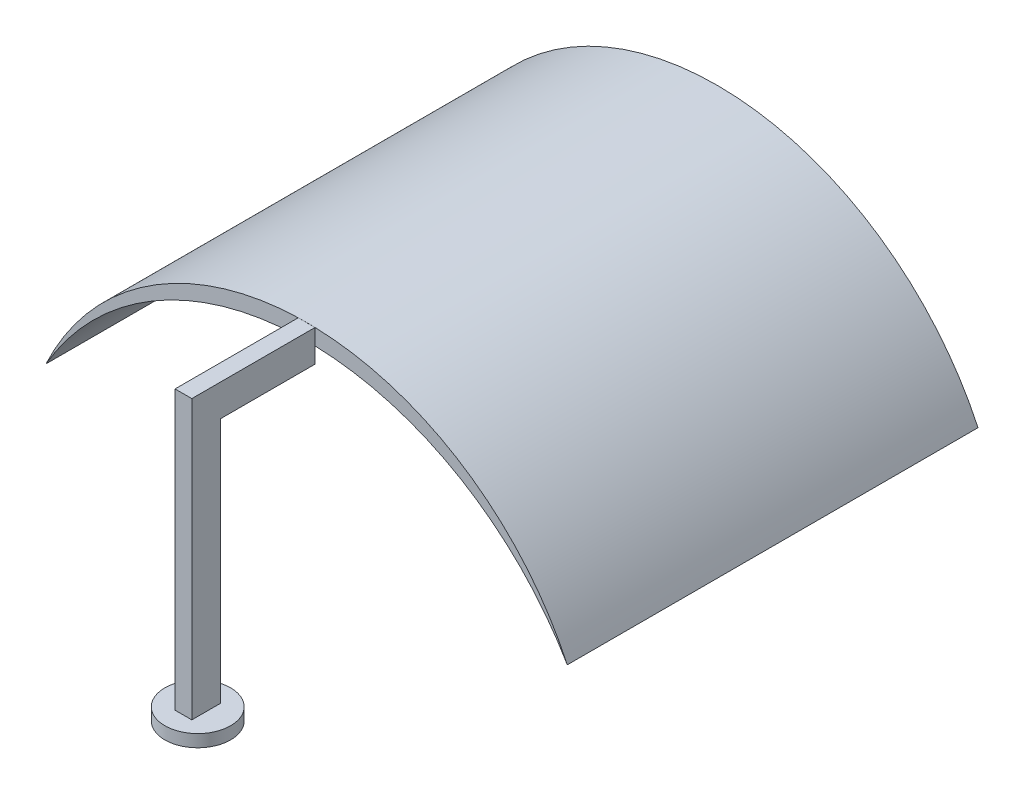
SolidWorks part; units mm, degrees
ref_plane "Front Plane" through (0, 0, 0) normal (0, 0, 1) x (1, 0, 0)
ref_plane "Top Plane" through (0, 0, 0) normal (0, 1, 0) x (1, 0, 0)
ref_plane "Right Plane" through (0, 0, 0) normal (1, 0, 0) x (0, 0, -1)
sketch "Sketch1" plane through (0, 0, 0) normal (0, 0, 1) x (1, 0, 0)
  line L0 (-350, 0) -> (350, 0) construction
  line L1 (-317.3107, 147.6954) -> (317.3107, 147.6954)
  circle A0 centre (0, 0) radius 350
  arc A1 (-317.3107, 147.6954) -> (317.3107, 147.6954) centre (0, -36.332) cw
  dimension "D1" = 700
extrude "Boss-Extrude1" add sketch "Sketch1" along normal blind 500 contours A0 A1 region at (0, 343.3391, 0)
sketch "Sketch2" plane through (0, 0, 500) normal (0, 0, 1) x (1, 0, 0)
  line L1 (-10.2038, 311.1118) -> (10.2038, 311.1118)
  line L2 (-10.2038, 311.1118) -> (-10.2038, 349.8512)
  line L3 (-10.2038, 349.8512) -> (10.2038, 349.8512)
  line L4 (10.2038, 311.1118) -> (10.2038, 349.8512)
  line L5 (-10.2038, 311.1118) -> (10.2038, 349.8512) construction
  line L6 (-10.2038, 349.8512) -> (10.2038, 311.1118) construction
  arc A0 (317.3107, 147.6954) -> (-317.3107, 147.6954) centre (0, -36.332) ccw construction
  arc A1 (317.3107, 147.6954) -> (-317.3107, 147.6954) centre (0, 0) ccw construction
  point P0 (0, 330.4815)
extrude "Boss-Extrude2" add sketch "Sketch2" along normal blind 150
sketch "Sketch3" plane through (0, 311.1118, 0) normal (0, -1, 0) x (1, 0, 0)
  line L0 (-10.2038, 650) -> (-10.2038, 500) construction
  line L1 (10.2038, 650) -> (-10.2038, 650)
  line L2 (10.2038, 650) -> (10.2038, 615.1603)
  line L3 (10.2038, 615.1603) -> (-10.2038, 615.1603)
  line L4 (-10.2038, 650) -> (-10.2038, 615.1603)
extrude "Boss-Extrude3" add sketch "Sketch3" along normal blind 300
sketch "Sketch4" plane through (0, 11.1118, 0) normal (0, -1, 0) x (1, 0, 0)
  line L0 (10.2038, 650) -> (-10.2038, 615.1603) construction
  circle A0 centre (0, 632.5802) radius 40
  dimension "D1" = 80
extrude "Boss-Extrude4" add sketch "Sketch4" along normal blind 15
